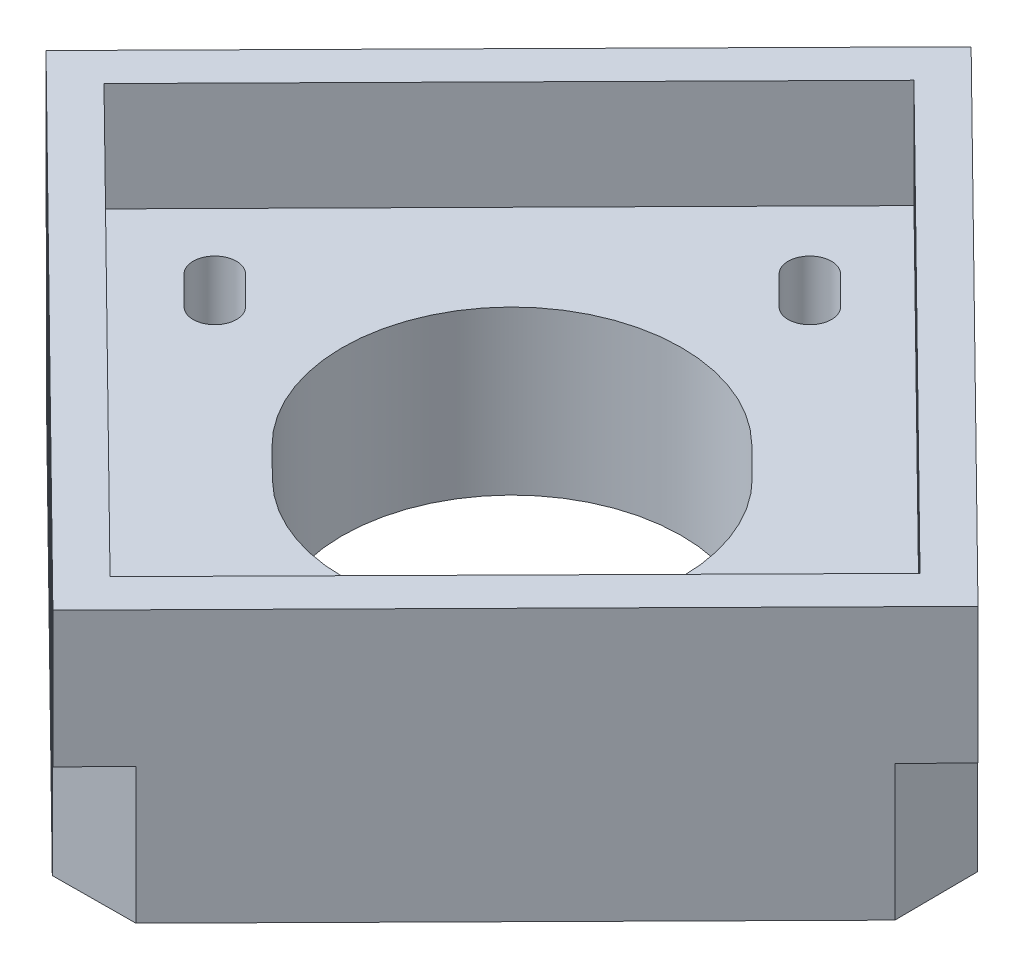
SolidWorks part; units mm, degrees
ref_plane "Front Plane" through (0, 0, 0) normal (0, 0, 1) x (1, 0, 0)
ref_plane "Top Plane" through (0, 0, 0) normal (0, 1, 0) x (1, 0, 0)
ref_plane "Right Plane" through (0, 0, 0) normal (1, 0, 0) x (0, 0, -1)
sketch "Sketch1" plane through (0, 0, 0) normal (0, 1, 0) x (1, 0, 0)
  line L1 (-107.5, -70) -> (107.5, -70)
  line L2 (-107.5, -70) -> (-107.5, 70)
  line L3 (-107.5, 70) -> (107.5, 70)
  line L4 (107.5, -70) -> (107.5, 70)
  line L5 (-107.5, -70) -> (107.5, 70) construction
  line L6 (-107.5, 70) -> (107.5, -70) construction
  point P0 (0, 0)
  dimension "D1" = 215
  dimension "D2" = 140
extrude "Boss-Extrude1" add sketch "Sketch1" along normal blind 10
fillet "Fillet1" radius 60 2 edges at (107.5, 5, -70) (107.5, 5, 70)
sketch "Sketch2" plane through (0, 10, 0) normal (0, 1, 0) x (1, 0, 0)
  line L0 (107.5, -10) -> (107.5, 10) construction
  line L1 (30.0949, 32.7279) -> (-38.981, 6.5456) construction
  line L2 (-38.981, -6.5456) -> (30.0949, -32.7279) construction
  circle A0 centre (42.5, 0) radius 20
  arc A1 (-38.981, 6.5456) -> (-38.981, -6.5456) centre (-36.5, 0) ccw construction
  circle A2 centre (-36.5, 0) radius 7.5
  arc A3 (30.0949, -32.7279) -> (30.0949, 32.7279) centre (42.5, 0) ccw construction
  dimension "D1" = 40
  dimension "D3" = 14
  dimension "D5" = 70
  dimension "D6" = 15
  dimension "D2" = 65
  dimension "D4" = 79
extrude "Cut-Extrude1" cut sketch "Sketch2" against normal through all
sketch "Sketch3" plane through (0, 10, 0) normal (0, 1, 0) x (1, 0, 0)
  line L0 (-36.5, 0) -> (-107.5, 70) construction
  line L1 (-67.0785, 38.2761) -> (-27.7732, 23.9602) construction
  line L2 (-75.2059, 30.0325) -> (-60.334, -9.0658) construction
  line L3 (-62.6172, 43.3029) -> (-60.4808, 41.1967)
  line L4 (-80.169, 25.5003) -> (-78.0327, 23.3941)
  arc A0 (-78.0327, 23.3941) -> (-60.4808, 41.1967) centre (-69.2568, 32.2954) ccw
  arc A1 (-67.0785, 38.2761) -> (-75.2059, 30.0325) centre (-69.2568, 32.2954) ccw construction
  arc A2 (-60.334, -9.0658) -> (-27.7732, 23.9602) centre (-36.5, 0) ccw construction
  arc A3 (-62.6172, 43.3029) -> (-80.169, 25.5003) centre (-71.3931, 34.4016) ccw
  dimension "D1" = 25
  dimension "D2" = 51
  dimension "D3" = 12.73
  dimension "D6" = 25
  dimension "D4" = 46
  dimension "D5" = 3
extrude "Cut-Extrude2" cut sketch "Sketch3" against normal through all
sketch "Sketch4" plane through (0, 10, 0) normal (0, 1, 0) x (1, 0, 0)
  line L0 (-47.3365, 32.2954) -> (-49.4578, 34.4167) construction
  line L1 (-91.1771, 32.2954) -> (-69.2568, 10.3751) construction
  line L2 (-91.1771, 32.2954) -> (-69.2568, 54.2157) construction
  line L3 (-69.2568, 54.2157) -> (-47.3365, 32.2954) construction
  line L4 (-69.2568, 10.3751) -> (-47.3365, 32.2954) construction
  line L5 (-91.1771, 32.2954) -> (-47.3365, 32.2954) construction
  line L6 (-69.2568, 54.2157) -> (-69.2568, 10.3751) construction
  line L7 (-48.4678, 31.164) -> (-50.5892, 33.2854)
  line L8 (-46.2051, 33.4268) -> (-48.3264, 35.5481)
  line L9 (-69.2568, 54.2157) -> (-71.3781, 56.337) construction
  line L10 (-70.3881, 53.0844) -> (-72.5095, 55.2057)
  line L11 (-68.1254, 55.3471) -> (-70.2467, 57.4684)
  line L12 (-69.2568, 10.3751) -> (-71.3781, 12.4964) construction
  line L13 (-70.3881, 9.2437) -> (-72.5095, 11.3651)
  line L14 (-68.1254, 11.5065) -> (-70.2467, 13.6278)
  line L15 (-91.1771, 32.2954) -> (-93.2984, 34.4167) construction
  line L16 (-92.3085, 31.164) -> (-94.4298, 33.2854)
  line L17 (-90.0457, 33.4268) -> (-92.167, 35.5481)
  line L18 (47.5, 70) -> (-107.5, 70) construction
  arc A0 (-48.4678, 31.164) -> (-46.2051, 33.4268) centre (-47.3365, 32.2954) ccw
  arc A1 (-48.3264, 35.5481) -> (-50.5892, 33.2854) centre (-49.4578, 34.4167) ccw
  arc A2 (-70.3881, 53.0844) -> (-68.1254, 55.3471) centre (-69.2568, 54.2157) ccw
  arc A3 (-70.2467, 57.4684) -> (-72.5095, 55.2057) centre (-71.3781, 56.337) ccw
  arc A4 (-70.3881, 9.2437) -> (-68.1254, 11.5065) centre (-69.2568, 10.3751) ccw
  arc A5 (-70.2467, 13.6278) -> (-72.5095, 11.3651) centre (-71.3781, 12.4964) ccw
  arc A6 (-92.3085, 31.164) -> (-90.0457, 33.4268) centre (-91.1771, 32.2954) ccw
  arc A7 (-92.167, 35.5481) -> (-94.4298, 33.2854) centre (-93.2984, 34.4167) ccw
  point P0 (-69.2568, 32.2954)
  point P6 (-48.3971, 33.3561)
  point P12 (-70.3174, 55.2764)
  point P18 (-70.3174, 11.4358)
  point P24 (-92.2377, 33.3561)
  dimension "D3" = 1.6
  dimension "D5" = 1.6
  dimension "D7" = 1.6
  dimension "D9" = 1.6
  dimension "D1" = 31
  dimension "D2" = 31
  dimension "D4" = 3
  dimension "D6" = 3
  dimension "D8" = 3
  dimension "D10" = 3
  dimension "D11" = 45
extrude "Cut-Extrude3" cut sketch "Sketch4" against normal through all
sketch "Sketch5" plane through (0, 10, 0) normal (0, 1, 0) x (1, 0, 0)
  circle A0 centre (-36.5, 0) radius 11
  dimension "D1" = 22
extrude "Cut-Extrude4" cut sketch "Sketch5" against normal blind 7
sketch "Sketch6" plane through (0, 0, 0) normal (0, -1, 0) x (1, 0, 0)
  circle A0 centre (-36.5, 0) radius 11
  circle A1 centre (-36.5, 0) radius 14
  dimension "D1" = 22
  dimension "D2" = 3
extrude "Boss-Extrude2" add sketch "Sketch6" along normal blind 8.5
sketch "Sketch7" plane through (0, 0, 0) normal (0, -1, 0) x (1, 0, 0)
  circle A0 centre (42.5, 0) radius 23.5
  dimension "D1" = 47
extrude "Cut-Extrude5" cut sketch "Sketch7" against normal blind 7
sketch "Sketch8" plane through (0, 0, 0) normal (0, -1, 0) x (1, 0, 0)
  circle A0 centre (42.5, 0) radius 30.5
  circle A1 centre (42.5, 0) radius 38.5
  dimension "D1" = 61
  dimension "D2" = 8
extrude "Boss-Extrude3" add sketch "Sketch8" along normal blind 8
sketch "Sketch9" plane through (0, 0, 0) normal (0, -1, 0) x (1, 0, 0)
  line L0 (47.5, 62) -> (-99.5, 62)
  line L1 (-99.5, 62) -> (-99.5, -62)
  line L2 (-99.5, -62) -> (47.5, -62)
  line L3 (99.5, -10) -> (99.5, 10)
  line L4 (-107.5, -70) -> (47.5, -70)
  line L5 (107.5, -10) -> (107.5, 10)
  line L6 (47.5, 70) -> (-107.5, 70)
  line L7 (-107.5, 70) -> (-107.5, -70)
  line L8 (-107.5, -70) -> (47.5, -70)
  line L9 (107.5, -10) -> (107.5, 10)
  line L10 (47.5, 70) -> (-107.5, 70)
  line L11 (-107.5, 70) -> (-107.5, -70)
  arc A0 (47.5, -62) -> (99.5, -10) centre (47.5, -10) ccw
  arc A1 (99.5, 10) -> (47.5, 62) centre (47.5, 10) ccw
  arc A2 (47.5, -70) -> (107.5, -10) centre (47.5, -10) ccw
  arc A3 (107.5, 10) -> (47.5, 70) centre (47.5, 10) ccw
  arc A4 (47.5, -70) -> (107.5, -10) centre (47.5, -10) ccw
  arc A5 (107.5, 10) -> (47.5, 70) centre (47.5, 10) ccw
  dimension "D1" = 0
  dimension "D2" = 8
extrude "Boss-Extrude4" add sketch "Sketch9" along normal blind 35
sketch "Sketch10" plane through (0, 0, 0) normal (0, -1, 0) x (1, 0, 0)
  line L0 (-36.5, -14) -> (-36.5, -62)
  line L1 (-99.5, -62) -> (47.5, -62) construction
  line L2 (-50.5, 0) -> (-99.5, 0)
  line L3 (-99.5, 62) -> (-99.5, -62) construction
  line L4 (-99.5, 0) -> (-99.5, -62)
  line L5 (-99.5, -62) -> (-36.5, -62)
  line L6 (-80.169, -25.5003) -> (-78.0327, -23.3941) construction
  line L7 (-80.169, -25.5003) -> (-78.0327, -23.3941)
  line L8 (-60.4808, -41.1967) -> (-62.6172, -43.3029) construction
  line L9 (-94.4298, -33.2854) -> (-92.3085, -31.164) construction
  line L10 (-90.0457, -33.4268) -> (-92.167, -35.5481) construction
  line L11 (-68.1254, -55.3471) -> (-70.2467, -57.4684) construction
  line L12 (-72.5095, -55.2057) -> (-70.3881, -53.0844) construction
  line L13 (-46.2051, -33.4268) -> (-48.3264, -35.5481) construction
  line L14 (-50.5892, -33.2854) -> (-48.4678, -31.164) construction
  line L15 (-68.1254, -11.5065) -> (-70.2467, -13.6278) construction
  line L16 (-72.5095, -11.3651) -> (-70.3881, -9.2437) construction
  line L17 (-60.4808, -41.1967) -> (-62.6172, -43.3029)
  line L18 (-94.4298, -33.2854) -> (-92.3085, -31.164)
  line L19 (-90.0457, -33.4268) -> (-92.167, -35.5481)
  line L20 (-68.1254, -55.3471) -> (-70.2467, -57.4684)
  line L21 (-72.5095, -55.2057) -> (-70.3881, -53.0844)
  line L22 (-46.2051, -33.4268) -> (-48.3264, -35.5481)
  line L23 (-50.5892, -33.2854) -> (-48.4678, -31.164)
  line L24 (-68.1254, -11.5065) -> (-70.2467, -13.6278)
  line L25 (-72.5095, -11.3651) -> (-70.3881, -9.2437)
  circle A0 centre (-36.5, 0) radius 14 construction
  circle A1 centre (-36.5, 0) radius 14 construction
  arc A2 (-50.5, 0) -> (-36.5, -14) centre (-36.5, 0) ccw
  arc A3 (-60.4808, -41.1967) -> (-78.0327, -23.3941) centre (-69.2568, -32.2954) ccw construction
  arc A4 (-80.169, -25.5003) -> (-62.6172, -43.3029) centre (-71.3931, -34.4016) ccw construction
  arc A5 (-90.0457, -33.4268) -> (-92.3085, -31.164) centre (-91.1771, -32.2954) ccw construction
  arc A6 (-94.4298, -33.2854) -> (-92.167, -35.5481) centre (-93.2984, -34.4167) ccw construction
  arc A7 (-72.5095, -55.2057) -> (-70.2467, -57.4684) centre (-71.3781, -56.337) ccw construction
  arc A8 (-68.1254, -55.3471) -> (-70.3881, -53.0844) centre (-69.2568, -54.2157) ccw construction
  arc A9 (-50.5892, -33.2854) -> (-48.3264, -35.5481) centre (-49.4578, -34.4167) ccw construction
  arc A10 (-46.2051, -33.4268) -> (-48.4678, -31.164) centre (-47.3365, -32.2954) ccw construction
  arc A11 (-72.5095, -11.3651) -> (-70.2467, -13.6278) centre (-71.3781, -12.4964) ccw construction
  arc A12 (-68.1254, -11.5065) -> (-70.3881, -9.2437) centre (-69.2568, -10.3751) ccw construction
  arc A13 (-60.4808, -41.1967) -> (-78.0327, -23.3941) centre (-69.2568, -32.2954) ccw
  arc A14 (-80.169, -25.5003) -> (-62.6172, -43.3029) centre (-71.3931, -34.4016) ccw
  arc A15 (-90.0457, -33.4268) -> (-92.3085, -31.164) centre (-91.1771, -32.2954) ccw
  arc A16 (-94.4298, -33.2854) -> (-92.167, -35.5481) centre (-93.2984, -34.4167) ccw
  arc A17 (-72.5095, -55.2057) -> (-70.2467, -57.4684) centre (-71.3781, -56.337) ccw
  arc A18 (-68.1254, -55.3471) -> (-70.3881, -53.0844) centre (-69.2568, -54.2157) ccw
  arc A19 (-50.5892, -33.2854) -> (-48.3264, -35.5481) centre (-49.4578, -34.4167) ccw
  arc A20 (-46.2051, -33.4268) -> (-48.4678, -31.164) centre (-47.3365, -32.2954) ccw
  arc A21 (-72.5095, -11.3651) -> (-70.2467, -13.6278) centre (-71.3781, -12.4964) ccw
  arc A22 (-68.1254, -11.5065) -> (-70.3881, -9.2437) centre (-69.2568, -10.3751) ccw
extrude "Boss-Extrude5" add sketch "Sketch10" along normal blind 8
sketch "Sketch11" plane through (0, 10, 0) normal (0, 1, 0) x (1, 0, 0)
  line L0 (-36.5, 0) -> (-107.5, 70) construction
  line L1 (-101.5171, 34.4708) -> (-71.8896, 64.5216)
  line L2 (-71.8896, 64.5216) -> (-40.2009, 33.2793)
  line L3 (-40.2009, 33.2793) -> (-69.8285, 3.2285)
  line L4 (-69.8285, 3.2285) -> (-101.5171, 34.4708)
  dimension "D1" = 42.2
  dimension "D2" = 44.5
  dimension "D3" = 26
  dimension "D4" = 21.1
extrude "Cut-Extrude6" cut sketch "Sketch11" against normal blind 8
sketch "Sketch12" plane through (0, 0, 0) normal (0, -1, 0) x (1, 0, 0)
  circle A0 centre (-36.5, 0) radius 7.5 construction
  circle A1 centre (-36.5, 0) radius 11
  circle A2 centre (-36.5, 0) radius 11
  circle A3 centre (-36.5, 0) radius 7.5
  dimension "D1" = 0
extrude "Boss-Extrude6" add sketch "Sketch12" along normal blind 0.5
sketch "Sketch14" plane through (0, -35, 0) normal (0, -1, 0) x (1, 0, 0)
  line L0 (99.5, -10) -> (99.5, 10) construction
  line L1 (99.5, -10) -> (99.5, 10)
  line L2 (42.5, 0) -> (99.5, 0) construction
  line L3 (42.5, 0) -> (95.1611, 21.813) construction
  line L4 (42.5, 0) -> (65.461, 55.4328) construction
  line L5 (60.3335, 57.5567) -> (61.3912, 60.1102)
  line L6 (70.5885, 53.3089) -> (71.7114, 56.0197)
  line L7 (93.0372, 26.9405) -> (96.1931, 28.2477)
  line L8 (97.285, 16.6854) -> (98.973, 17.3846)
  arc A0 (47.5, -62) -> (99.5, -10) centre (47.5, -10) ccw construction
  arc A1 (99.5, 10) -> (47.5, 62) centre (47.5, 10) ccw construction
  arc A2 (47.5, -62) -> (99.5, -10) centre (47.5, -10) ccw
  arc A3 (99.5, 10) -> (47.5, 62) centre (47.5, 10) ccw
  circle A4 centre (65.461, 55.4328) radius 2.05
  circle A5 centre (95.1611, 21.813) radius 2.05
  arc A6 (60.3335, 57.5567) -> (70.5885, 53.3089) centre (65.461, 55.4328) ccw
  arc A7 (93.0372, 26.9405) -> (97.285, 16.6854) centre (95.1611, 21.813) ccw
  circle A8 centre (65.461, 55.4328) radius 5.55 construction
  circle A9 centre (95.1611, 21.813) radius 5.55 construction
  arc M12 (47.5, 62) -> (99.5, 10) centre (47.5, 10) cw
  dimension "D5" = 4.1
  dimension "D6" = 4.1
  dimension "D1" = 22.5
  dimension "D2" = 67.5
  dimension "D3" = 57
  dimension "D4" = 60
  dimension "D7" = 3.5
extrude "Boss-Extrude7" add sketch "Sketch14" against normal up to next contours L5 A6 L6 A4 M12 | L7 A7 L8 A5 M12 region at (97.7294, -35, 22.8536) region at (61.0066, -35, 58.7737)
ref_plane "Plane1" through (0, -25, 0) normal (0, -1, 0) x (-1, 0, 0)
sketch "Sketch15" plane through (0, -25, 0) normal (0, -1, 0) x (-1, 0, 0)
  line L0 (-70.5885, -53.3089) -> (-71.7114, -56.0197) construction
  line L1 (-92.6363, -16.8705) -> (-98.459, -19.2824)
  line L2 (-98.459, -19.2824) -> (-99.0016, -23.4037)
  line L3 (-99.0016, -23.4037) -> (-95.7037, -25.9343)
  line L4 (-95.7037, -25.9343) -> (-89.881, -23.5225)
  line L7 (-67.1705, -50.1526) -> (-69.5824, -55.9754)
  line L8 (-69.5824, -55.9754) -> (-67.0518, -59.2733)
  line L9 (-67.0518, -59.2733) -> (-62.9304, -58.7307)
  line L10 (-62.9304, -58.7307) -> (-60.5186, -52.9079)
  line L13 (-98.973, -17.3846) -> (-97.285, -16.6854) construction
  line L14 (-91.3206, -20.2222) -> (-92.9696, -18.9569) [skipped]
  line L15 (-91.8632, -24.3435) -> (-91.5919, -22.2828) [skipped]
  line L16 (-61.3396, -54.8902) -> (-62.6049, -53.2412) [skipped]
  line L17 (-65.9309, -51.8636) -> (-67.9916, -52.1349) [skipped]
  circle A0 centre (-95.1611, -21.813) radius 3.6 construction
  circle A1 centre (-65.461, -55.4328) radius 3.6 construction
  arc A2 (-60.3335, -57.5567) -> (-70.5885, -53.3089) centre (-65.461, -55.4328) ccw construction
  arc A3 (-60.5186, -52.9079) -> (-67.1705, -50.1526) centre (-65.461, -55.4328) ccw
  arc A4 (-93.0372, -26.9405) -> (-97.285, -16.6854) centre (-95.1611, -21.813) ccw construction
  arc A5 (-89.881, -23.5225) -> (-92.6363, -16.8705) centre (-95.1611, -21.813) ccw
  dimension "D1" = 7.2
  dimension "D2" = 7.2
extrude "Cut-Extrude7" cut sketch "Sketch15" against normal blind 3.6
mirror "Mirror1" about plane through (0, 0, 0) normal (0, 0, 1) of "Cut-Extrude7", "Boss-Extrude7"
sketch "Sketch16" plane through (0, -35, 0) normal (0, -1, 0) x (1, 0, 0)
  line L0 (42.5, 0) -> (0, 0) construction
  line L1 (22.5, 0) -> (22.5, 59) construction
  line L2 (16.95, 59) -> (16.95, 62)
  line L3 (47.5, 62) -> (-99.5, 62) construction
  line L4 (16.95, 62) -> (28.05, 62)
  line L5 (47.5, 62) -> (-99.5, 62) construction
  line L6 (28.05, 62) -> (28.05, 59)
  circle A0 centre (22.5, 59) radius 2.05
  arc A1 (16.95, 59) -> (28.05, 59) centre (22.5, 59) ccw
  circle A2 centre (22.5, 59) radius 5.55 construction
  dimension "D3" = 4.1
  dimension "D1" = 59
  dimension "D2" = 20
  dimension "D4" = 3.5
extrude "Boss-Extrude8" add sketch "Sketch16" against normal up to next
sketch "Sketch17" plane through (0, -25, 0) normal (0, -1, 0) x (-1, 0, 0)
  line L0 (-16.95, -59) -> (-16.95, -62) construction
  line L3 (-26.1, -54.776) -> (-26.1, -61.0785)
  line L4 (-26.1, -61.0785) -> (-22.5, -63.1569)
  line L5 (-22.5, -63.1569) -> (-18.9, -61.0785)
  line L6 (-18.9, -61.0785) -> (-18.9, -54.776)
  line L7 (-20.7, -55.8823) -> (-22.5, -54.8431) [skipped]
  line L8 (-24.3, -55.8823) -> (-26.1, -56.9215) [skipped]
  arc A1 (-16.95, -59) -> (-28.05, -59) centre (-22.5, -59) ccw construction
  arc A2 (-16.95, -59) -> (-28.05, -59) centre (-22.5, -59) ccw
  dimension "D1" = 7.2
extrude "Cut-Extrude8" cut sketch "Sketch17" against normal blind 3.6 contours L6 A2 L3 L4 L5 region at (22.5, -25, 58.0058)
pattern_linear "LPattern1" count 3 spacing 55 along (-1, 0, 0) of "Cut-Extrude8", "Boss-Extrude8"
mirror "Mirror2" about plane through (0, 0, 0) normal (0, 0, 1) of "LPattern1", "Boss-Extrude8", "Cut-Extrude8"
sketch "Sketch18" plane through (0, -35, 0) normal (0, -1, 0) x (1, 0, 0)
  line L0 (-107.5, 70) -> (-107.5, -70) construction
  line L1 (-96.5, 28.55) -> (-99.5, 28.55)
  line L2 (-99.5, 62) -> (-99.5, -62) construction
  line L3 (-99.5, 28.55) -> (-99.5, 17.45)
  line L4 (-99.5, 17.45) -> (-96.5, 17.45)
  circle A0 centre (-96.5, 23) radius 2.05
  arc A1 (-96.5, 17.45) -> (-96.5, 28.55) centre (-96.5, 23) ccw
  circle A2 centre (-96.5, 23) radius 5.55 construction
  dimension "D1" = 4.1
  dimension "D3" = 23
  dimension "D4" = 11
  dimension "D2" = 3.5
extrude "Boss-Extrude9" add sketch "Sketch18" against normal up to next
sketch "Sketch19" plane through (0, -25, 0) normal (0, -1, 0) x (-1, 0, 0)
  line L0 (99.5, -17.45) -> (96.5, -17.45) construction
  line L1 (98.5785, -19.4) -> (92.276, -19.4)
  line L4 (92.276, -26.6) -> (98.5785, -26.6)
  line L5 (98.5785, -26.6) -> (100.6569, -23)
  line L6 (100.6569, -23) -> (98.5785, -19.4)
  line L7 (92.3431, -23) -> (93.3823, -24.8) [skipped]
  line L8 (94.4215, -19.4) -> (93.3823, -21.2) [skipped]
  circle A0 centre (96.5, -23) radius 3.6 construction
  arc A1 (96.5, -17.45) -> (96.5, -28.55) centre (96.5, -23) ccw construction
  arc A2 (92.276, -19.4) -> (92.276, -26.6) centre (96.5, -23) ccw
  dimension "D1" = 7.2
extrude "Cut-Extrude9" cut sketch "Sketch19" against normal blind 3.6
mirror "Mirror3" about plane through (0, 0, 0) normal (0, 0, 1) of "Boss-Extrude9", "Cut-Extrude9"
sketch "Sketch20" plane through (0, 0, 0) normal (0, -1, 0) x (1, 0, 0)
  line L0 (-26.95, -62) -> (16.95, -62) construction
  line L1 (45.3284, 2.8284) -> (-16.6716, 64.8284) construction
  line L2 (28.05, -62) -> (47.5, -62) construction
  line L3 (99.5, -10) -> (99.5, 10) construction
  line L4 (45.3284, -2.8284) -> (-16.6716, -64.8284) construction
  line L5 (47.5, 62) -> (28.05, 62) construction
  line L7 (16.95, 62) -> (-26.95, 62) construction
  line L8 (-26.95, -62) -> (16.95, -62)
  line L10 (28.05, -62) -> (47.5, -62)
  line L12 (99.5, -10) -> (99.5, 10)
  line L13 (47.5, 62) -> (28.05, 62)
  line L14 (16.95, 62) -> (-26.95, 62)
  line L15 (42.5, 0) -> (99.5, 0) construction
  line L16 (42.5, 0) -> (86.6845, 44.1845) construction
  line L17 (42.5, 0) -> (86.6845, -44.1845) construction
  line L18 (42.5, 0) -> (-19.5, -62) construction
  line L19 (42.5, 0) -> (-19.5, 62) construction
  line L20 (42.5, 0) -> (42.5, 62) construction
  line L21 (42.5, 0) -> (42.5, -62) construction
  line L22 (45.3284, 2.8284) -> (-13.8431, 62)
  line L23 (46.5, 0) -> (46.5, 62)
  line L24 (45.3284, -2.8284) -> (89.5129, 41.356)
  line L25 (42.5, -4) -> (99.5, -4)
  line L26 (39.6716, -2.8284) -> (83.9397, -47.0965)
  line L27 (38.5, 0) -> (38.5, -62)
  line L28 (39.6716, 2.8284) -> (-25.1569, -62)
  line L29 (39.6716, -2.8284) -> (-25.1569, 62)
  line L30 (38.5, 0) -> (38.5, 62)
  line L31 (39.6716, 2.8284) -> (83.9397, 47.0965)
  line L32 (42.5, 4) -> (99.5, 4)
  line L33 (45.3284, 2.8284) -> (89.5129, -41.356)
  line L34 (46.5, 0) -> (46.5, -62)
  line L35 (45.3284, -2.8284) -> (-13.8431, -62)
  line L36 (39.6716, -2.8284) -> (-22.3284, 59.1716) construction
  line L37 (39.6716, 2.8284) -> (-22.3284, -59.1716) construction
  line L38 (39.6716, -2.8284) -> (83.856, -47.0129) construction
  line L39 (39.6716, 2.8284) -> (83.856, 47.0129) construction
  circle A0 centre (42.5, 0) radius 38.5
  circle A1 centre (42.5, 0) radius 38.5 construction
  arc A2 (71.7114, -56.0197) -> (96.1931, -28.2477) centre (47.5, -10) ccw construction
  arc A3 (96.1931, 28.2477) -> (71.7114, 56.0197) centre (47.5, 10) ccw construction
  arc A4 (71.7114, -56.0197) -> (96.1931, -28.2477) centre (47.5, -10) ccw
  arc A5 (96.1931, 28.2477) -> (71.7114, 56.0197) centre (47.5, 10) ccw
  arc M32 (71.7114, -56.0197) -> (96.1931, -28.2477) centre (47.5, -10) ccw
  arc M42 (96.1931, 28.2477) -> (71.7114, 56.0197) centre (47.5, 10) ccw
  circle M63 centre (42.5, 0) radius 38.5
  dimension "D1" = 45
  dimension "D2" = 45
  dimension "D3" = 45
  dimension "D4" = 45
  dimension "D5" = 4
  dimension "D6" = 4
extrude "Boss-Extrude10" add sketch "Sketch20" along normal up to surface (8 mm away) contours L29 L22 L14 M63 | L30 L23 L13 M63 | L31 L24 M63 M42 | L32 L25 L12 M63 | L33 L26 M63 M32 | L34 L27 L10 M63 | L35 L28 L8 M63 region at (-2.2021, 0, -44.549) region at (-2.2021, 0, 44.549) region at (42.5, 0, -50.2152) region at (42.5, 0, 50.2152) region at (78.1509, 0, -35.6723) region at (78.1509, 0, 35.6723) region at (90.2152, 0, 0) up to face at (42.5, -8, -38.5)
sketch "Sketch21" plane through (0, 0, 0) normal (0, -1, 0) x (1, 0, 0)
  line L0 (-2.5, 12) -> (-2.5, 24) construction
  line L1 (-5, 12) -> (-5, 24)
  line L2 (0, 12) -> (0, 24)
  line L3 (-2.5, -12) -> (-2.5, -24) construction
  line L4 (0, -12) -> (0, -24)
  line L5 (-5, -12) -> (-5, -24)
  arc A0 (-5, 12) -> (0, 12) centre (-2.5, 12) ccw
  arc A1 (0, 24) -> (-5, 24) centre (-2.5, 24) ccw
  arc A2 (0, -12) -> (-5, -12) centre (-2.5, -12) ccw
  arc A3 (-5, -24) -> (0, -24) centre (-2.5, -24) ccw
  circle A4 centre (-36.5, 0) radius 7.5 construction
  point P2 (-2.5, 18)
  point P7 (-2.5, -18)
  dimension "D1" = 2.5
  dimension "D2" = 2.5
  dimension "D5" = 34
  dimension "D3" = 12
  dimension "D4" = 12
  dimension "D6" = 12
  dimension "D7" = 12
extrude "Cut-Extrude10" cut sketch "Sketch21" against normal through all
sketch "Sketch22" plane through (0, 0, 0) normal (0, -1, 0) x (1, 0, 0)
  line L0 (-13.888, 2.46) -> (-5.5, -2) construction
  line L1 (-81.95, -62) -> (-38.05, -62) construction
  circle A0 centre (-5.5, -2) radius 1.6
  circle A1 centre (-13.888, 2.46) radius 1.6
  circle A2 centre (-36.5, 0) radius 7.5 construction
  dimension "D4" = 3.2
  dimension "D5" = 3.2
  dimension "D1" = 31
  dimension "D2" = 2
  dimension "D3" = 9.5
  dimension "D6" = 28
extrude "Cut-Extrude11" cut sketch "Sketch22" against normal through all
sketch "Sketch23" plane through (0, 0, 0) normal (0, -1, 0) x (1, 0, 0)
  line L0 (-99.5, 17.45) -> (-99.5, -17.45) construction
  line L1 (-50.5, 0) -> (-99.5, 0) construction
  line L2 (-36.5, -55.1526) -> (-36.5, -14) construction
  line L3 (-26.95, -62) -> (16.95, -62) construction
  circle A0 centre (-87.5, 8) radius 2.05
  circle A1 centre (-75.5, 8) radius 2.05
  circle A2 centre (-28.5, -36) radius 2.05
  circle A3 centre (-28.5, -48) radius 2.05
  circle A4 centre (-16.5, -42) radius 2.05
  dimension "D4" = 4.1
  dimension "D5" = 4.1
  dimension "D6" = 4.1
  dimension "D7" = 4.1
  dimension "D8" = 4.1
  dimension "D1" = 12
  dimension "D2" = 12
  dimension "D3" = 8
  dimension "D9" = 8
  dimension "D10" = 12
  dimension "D11" = 20
  dimension "D12" = 20
  dimension "D13" = 14
extrude "Cut-Extrude12" cut sketch "Sketch23" against normal through all
sketch "Sketch24" plane through (-107.5, 0, 0) normal (-1, 0, 0) x (0, 0, 1)
  line L0 (70, -35) -> (-70, -35) construction
  line L1 (70, 10) -> (70, -35) construction
  line L2 (-70, 10) -> (-70, -35) construction
  circle A0 centre (0, -27) radius 2.05
  circle A1 centre (0, -13) radius 2.05
  circle A2 centre (-50, -13) radius 2.05
  circle A3 centre (-50, -27) radius 2.05
  circle A4 centre (50, -13) radius 2.05
  circle A5 centre (50, -27) radius 2.05
  dimension "D1" = 4.1
  dimension "D2" = 4.1
  dimension "D5" = 4.1
  dimension "D6" = 4.1
  dimension "D8" = 4.1
  dimension "D9" = 4.1
  dimension "D3" = 8
  dimension "D4" = 14
  dimension "D7" = 20
  dimension "D10" = 20
extrude "Cut-Extrude13" cut sketch "Sketch24" against normal up to next
sketch "Croquis1" plane through (0, 10, 0) normal (0, 1, 0) x (1, 0, 0)
  line L8 (-35.9584, 33.3094) -> (-71.9196, 68.7642)
  line L9 (-71.9196, 68.7642) -> (-105.7596, 34.4408)
  line L10 (-105.7596, 34.4408) -> (-69.7984, -1.014)
  line L11 (-69.7984, -1.014) -> (-35.9584, 33.3094)
  line L12 (-35.9584, 33.3094) -> (-71.9196, 68.7642)
  line L13 (-71.9196, 68.7642) -> (-105.7596, 34.4408)
  line L14 (-105.7596, 34.4408) -> (-69.7984, -1.014)
  line L15 (-69.7984, -1.014) -> (-35.9584, 33.3094)
  dimension "D1" = 3
extrude "Cortar-Extruir1" cut sketch "Croquis1" against normal through all flip side to cut
sketch "Croquis2" plane through (-34.9111, 0, 35.4099) normal (-0.7021, 0, 0.7121) x (0.7121, 0, 0.7021)
  line L0 (-48.9918, -8) -> (-99.4918, -8)
  line L1 (-99.4918, -8) -> (-99.4918, 10)
  line L2 (-99.4918, 10) -> (-48.9918, 10)
  line L3 (-48.9918, 10) -> (-48.9918, -8)
extrude "Cortar-Extruir2" cut sketch "Croquis2" against normal through all both and the other way through all flip side to cut
sketch "Croquis3" plane through (0, -8, 0) normal (0, -1, 0) x (1, 0, 0)
  line L0 (-74.9594, -65.6809) -> (-102.7198, -37.524)
  line L2 (-71.9196, -68.7642) -> (-36.5, -33.8434) construction
  line L4 (-70.8269, 0) -> (-105.7596, -34.4408) construction
  line L5 (-105.7596, -34.4408) -> (-71.9196, -68.7642) construction
  line L6 (-102.6764, -31.401) -> (-102.7198, -37.524)
  line L7 (-68.8364, -65.7244) -> (-74.9594, -65.6809)
  line L12 (-68.8364, -65.7244) -> (-39.0416, -36.3492)
  line L13 (-71.9196, -68.7642) -> (-36.5, -33.8434) construction
  line L14 (-39.0416, -36.3492) -> (-38.9982, -30.2262)
  line L15 (-36.5, -32.7601) -> (-68.7987, 0) construction
  line L16 (-38.9982, -30.2262) -> (-66.7586, -2.0692)
  line L17 (-66.7586, -2.0692) -> (-72.8816, -2.0258)
  line L18 (-72.8816, -2.0258) -> (-102.6764, -31.401)
  point P15 (-88.8396, -51.6025)
  dimension "D1" = 135
  dimension "D2" = 135
  dimension "D3" = 135
  dimension "D4" = 135
  dimension "D5" = 6.123
extrude "Cortar-Extruir3" cut sketch "Croquis3" against normal blind 8 and the other way through all flip side to cut
sketch "Croquis6" plane through (-34.9111, 0, 35.4099) normal (-0.7021, 0, 0.7121) x (0.7121, 0, 0.7021)
  line L0 (-99.4918, -7) -> (-48.9918, -7)
  line L3 (-48.9918, -7) -> (-48.9918, -8)
  line L4 (-48.9918, -8) -> (-99.4918, -8)
  line L5 (-99.4918, -8) -> (-99.4918, -7)
  dimension "D1" = 1
sketch "Croquis7" plane through (0, -8, 0) normal (0, -1, 0) x (1, 0, 0)
  line L0 (-70.3881, -9.2437) -> (-72.5095, -11.3651) construction
  line L1 (-70.2467, -13.6278) -> (-68.1254, -11.5065) construction
  line L2 (-92.167, -35.5481) -> (-90.0457, -33.4268) construction
  line L3 (-92.3085, -31.164) -> (-94.4298, -33.2854) construction
  line L4 (-70.2467, -57.4684) -> (-68.1254, -55.3471) construction
  line L6 (-48.3264, -35.5481) -> (-46.2051, -33.4268) construction
  line L7 (-48.4678, -31.164) -> (-50.5892, -33.2854) construction
  line L8 (-102.6764, -31.401) -> (-102.7198, -37.524)
  line L9 (-102.7198, -37.524) -> (-74.9594, -65.6809)
  line L10 (-74.9594, -65.6809) -> (-68.8364, -65.7244)
  line L11 (-68.8364, -65.7244) -> (-39.0416, -36.3492)
  line L12 (-39.0416, -36.3492) -> (-38.9982, -30.2262)
  line L13 (-38.9982, -30.2262) -> (-66.7586, -2.0692)
  line L14 (-66.7586, -2.0692) -> (-72.8816, -2.0258)
  line L15 (-72.8816, -2.0258) -> (-102.6764, -31.401)
  line L16 (-102.6764, -31.401) -> (-102.7198, -37.524)
  line L17 (-102.7198, -37.524) -> (-74.9594, -65.6809)
  line L18 (-74.9594, -65.6809) -> (-68.8364, -65.7244)
  line L19 (-68.8364, -65.7244) -> (-39.0416, -36.3492)
  line L20 (-39.0416, -36.3492) -> (-38.9982, -30.2262)
  line L21 (-38.9982, -30.2262) -> (-66.7586, -2.0692)
  line L22 (-66.7586, -2.0692) -> (-72.8816, -2.0258)
  line L23 (-72.8816, -2.0258) -> (-102.6764, -31.401)
  line L24 (-48.4678, -31.164) -> (-50.5892, -33.2854)
  line L25 (-48.3264, -35.5481) -> (-46.2051, -33.4268)
  line L26 (-70.2467, -57.4684) -> (-68.1254, -55.3471)
  line L27 (-92.3085, -31.164) -> (-94.4298, -33.2854)
  line L28 (-92.167, -35.5481) -> (-90.0457, -33.4268)
  line L29 (-70.2467, -13.6278) -> (-68.1254, -11.5065)
  line L30 (-70.3881, -9.2437) -> (-72.5095, -11.3651)
  arc A0 (-68.1254, -11.5065) -> (-70.3881, -9.2437) centre (-69.2568, -10.3751) ccw construction
  arc A1 (-72.5095, -11.3651) -> (-70.2467, -13.6278) centre (-71.3781, -12.4964) ccw construction
  arc A2 (-94.4298, -33.2854) -> (-92.167, -35.5481) centre (-93.2984, -34.4167) ccw construction
  arc A3 (-90.0457, -33.4268) -> (-92.3085, -31.164) centre (-91.1771, -32.2954) ccw construction
  arc A4 (-72.5095, -55.2057) -> (-70.2467, -57.4684) centre (-71.3781, -56.337) ccw construction
  arc A5 (-68.1254, -55.3471) -> (-70.3881, -53.0844) centre (-69.2568, -54.2157) ccw construction
  arc A6 (-50.5892, -33.2854) -> (-48.3264, -35.5481) centre (-49.4578, -34.4167) ccw construction
  arc A7 (-46.2051, -33.4268) -> (-48.4678, -31.164) centre (-47.3365, -32.2954) ccw construction
  arc A8 (-46.2051, -33.4268) -> (-48.4678, -31.164) centre (-47.3365, -32.2954) ccw
  arc A9 (-50.5892, -33.2854) -> (-48.3264, -35.5481) centre (-49.4578, -34.4167) ccw
  arc A10 (-68.1254, -55.3471) -> (-70.3881, -53.0844) centre (-69.2568, -54.2157) ccw
  arc A11 (-72.5095, -55.2057) -> (-70.2467, -57.4684) centre (-71.3781, -56.337) ccw
  arc A12 (-90.0457, -33.4268) -> (-92.3085, -31.164) centre (-91.1771, -32.2954) ccw
  arc A13 (-94.4298, -33.2854) -> (-92.167, -35.5481) centre (-93.2984, -34.4167) ccw
  arc A14 (-72.5095, -11.3651) -> (-70.2467, -13.6278) centre (-71.3781, -12.4964) ccw
  arc A15 (-68.1254, -11.5065) -> (-70.3881, -9.2437) centre (-69.2568, -10.3751) ccw
  line M9 (-102.6764, -31.401) -> (-102.7198, -37.524)
  line M10 (-102.7198, -37.524) -> (-74.9594, -65.6809)
  line M11 (-74.9594, -65.6809) -> (-68.8364, -65.7244)
  line M12 (-68.8364, -65.7244) -> (-39.0416, -36.3492)
  line M13 (-39.0416, -36.3492) -> (-38.9982, -30.2262)
  line M14 (-38.9982, -30.2262) -> (-66.7586, -2.0692)
  line M15 (-66.7586, -2.0692) -> (-72.8816, -2.0258)
  line M16 (-72.8816, -2.0258) -> (-102.6764, -31.401)
  line M17 (-60.4808, -41.1967) -> (-62.6172, -43.3029)
  arc M18 (-62.6172, -43.3029) -> (-80.169, -25.5003) centre (-71.3931, -34.4016) cw
  line M19 (-80.169, -25.5003) -> (-78.0327, -23.3941)
  arc M20 (-78.0327, -23.3941) -> (-60.4808, -41.1967) centre (-69.2568, -32.2954) cw
  line M21 (-94.4298, -33.2854) -> (-92.3085, -31.164)
  arc M22 (-92.3085, -31.164) -> (-90.0457, -33.4268) centre (-91.1771, -32.2954) cw
  line M23 (-90.0457, -33.4268) -> (-92.167, -35.5481)
  arc M24 (-92.167, -35.5481) -> (-94.4298, -33.2854) centre (-93.2984, -34.4167) cw
  line M25 (-72.5095, -55.2057) -> (-70.3881, -53.0844)
  arc M26 (-70.3881, -53.0844) -> (-68.1254, -55.3471) centre (-69.2568, -54.2157) cw
  line M27 (-68.1254, -55.3471) -> (-70.2467, -57.4684)
  arc M28 (-70.2467, -57.4684) -> (-72.5095, -55.2057) centre (-71.3781, -56.337) cw
  line M29 (-50.5892, -33.2854) -> (-48.4678, -31.164)
  arc M30 (-48.4678, -31.164) -> (-46.2051, -33.4268) centre (-47.3365, -32.2954) cw
  line M31 (-46.2051, -33.4268) -> (-48.3264, -35.5481)
  arc M32 (-48.3264, -35.5481) -> (-50.5892, -33.2854) centre (-49.4578, -34.4167) cw
  line M33 (-68.1254, -11.5065) -> (-70.2467, -13.6278)
  arc M34 (-70.2467, -13.6278) -> (-72.5095, -11.3651) centre (-71.3781, -12.4964) cw
  line M35 (-72.5095, -11.3651) -> (-70.3881, -9.2437)
  arc M36 (-70.3881, -9.2437) -> (-68.1254, -11.5065) centre (-69.2568, -10.3751) cw
  dimension "D1" = 0
extrude "Saliente-Extruir1" add sketch "Croquis7" along normal blind 2 contours M16 M9 M10 M11 M12 M13 M14 M15 M20 M17 M18 M19 M24 M21 M22 M23 M28 M25 M26 M27 M32 M29 M30 M31 M36 M33 M34 M35 region at (-87.1464, -8, -17.355)
